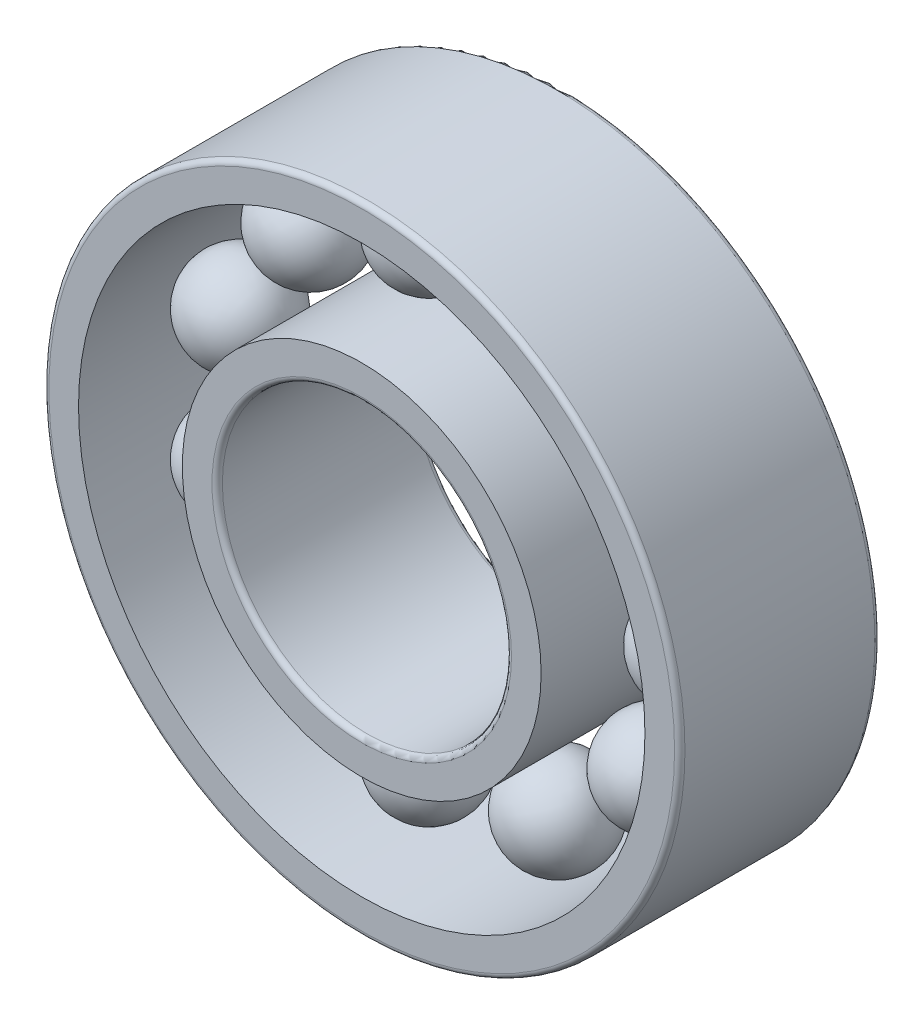
SolidWorks part; units mm, degrees
ref_plane "Front Plane" through (0, 0, 0) normal (0, 0, 1) x (1, 0, 0)
ref_plane "Top Plane" through (0, 0, 0) normal (0, 1, 0) x (1, 0, 0)
ref_plane "Right Plane" through (0, 0, 0) normal (1, 0, 0) x (0, 0, -1)
sketch "S" plane through (0, 0, 0) normal (0, 0, 1) x (1, 0, 0)
  line L0 (-5.5, 0) -> (5.5, 0) construction
  circle A0 centre (0, 0) radius 7.9375 construction
  circle A1 centre (0, 0) radius 17.4625 construction
  circle A2 centre (0, 0) radius 9.85 construction
  circle A3 centre (0, 0) radius 15.55 construction
  dimension "ID" = 15.875
  dimension "OD" = 34.925
  dimension "IDa" = 19.7
  dimension "ODa" = 31.1
  dimension "B" = 11
ref_axis "Z" through (0, 0, -6.05) along (0, 0, 1)
sketch "InnerS" plane through (0, 0, 0) normal (0, 1, 0) x (1, 0, 0)
  line L0 (7.9375, -5.5) -> (9.85, -5.5)
  line L1 (9.85, -5.5) -> (9.85, 5.5)
  line L2 (9.85, 5.5) -> (7.9375, 5.5)
  line L3 (7.9375, 5.5) -> (7.9375, -5.5)
  line L4 (0, -9.25) -> (0, 9.25) construction
  dimension "r1" = 7.9375
  dimension "r2" = 9.85
  dimension "z1" = 5.5
  dimension "z2" = 5.5
revolve "InnerRing" add sketch "InnerS" angle 360 about L4
sketch "OuterS" plane through (0, 0, 0) normal (0, 1, 0) x (1, 0, 0)
  line L0 (15.55, -5.5) -> (17.4625, -5.5)
  line L1 (17.4625, -5.5) -> (17.4625, 5.5)
  line L2 (17.4625, 5.5) -> (15.55, 5.5)
  line L3 (15.55, 5.5) -> (15.55, -5.5)
  line L4 (0, -9.25) -> (0, 9.25) construction
  dimension "r1" = 15.55
  dimension "r2" = 17.4625
  dimension "z1" = 5.5
  dimension "z2" = 5.5
revolve "OuterRing" add sketch "OuterS" angle 360 about L4
sketch "BallS" plane through (0, 0, 0) normal (0, 1, 0) x (1, 0, 0)
  line L0 (9.9925, 0) -> (15.4075, 0)
  arc A0 (9.9925, 0) -> (15.4075, 0) centre (12.7, 0) ccw
  dimension "r" = 2.7075
  dimension "p" = 12.7
revolve "Ball" add sketch "BallS" angle 360 about L0
pattern_circular "BallsPattern" count 11 over 360 about axis through (0, 0, -6.05) along (0, 0, 1) of bodies 103
fillet "F1" radius 0.2858 2 edges at (17.4625, 0, -5.5) (17.4625, 0, 5.5)
fillet "F2" radius 0.2858 2 edges at (7.9375, 0, -5.5) (7.9375, 0, 5.5)
equation "\"r1@InnerS\" = abs(0.5*\"ID@S\")"
equation "\"r2@InnerS\" = abs(0.5*\"IDa@S\")"
equation "\"z1@InnerS\" = abs(-0.5*\"B@S\")"
equation "\"z2@InnerS\" = abs(0.5*\"B@S\")"
equation "\"r1@OuterS\" = abs(0.5*\"ODa@S\")"
equation "\"r2@OuterS\" = abs(0.5*\"OD@S\")"
equation "\"z1@OuterS\" = abs(-0.5*\"B@S\")"
equation "\"z2@OuterS\" = abs(0.5*\"B@S\")"
equation "\"r@BallS\" = abs(0.2375*\"ODa@S\"-0.2375*\"IDa@S\")"
equation "\"p@BallS\" = abs(0.25*\"IDa@S\"+0.25*\"ODa@S\")"
equation "\"N@BallsPattern\" = int(2.417*(0.25*\"IDa@S\"+0.25*\"ODa@S\")/(0.2375*\"ODa@S\"-0.2375*\"IDa@S\"))"
equation "\"r_min@F2\" = \"r_min@F1\""
